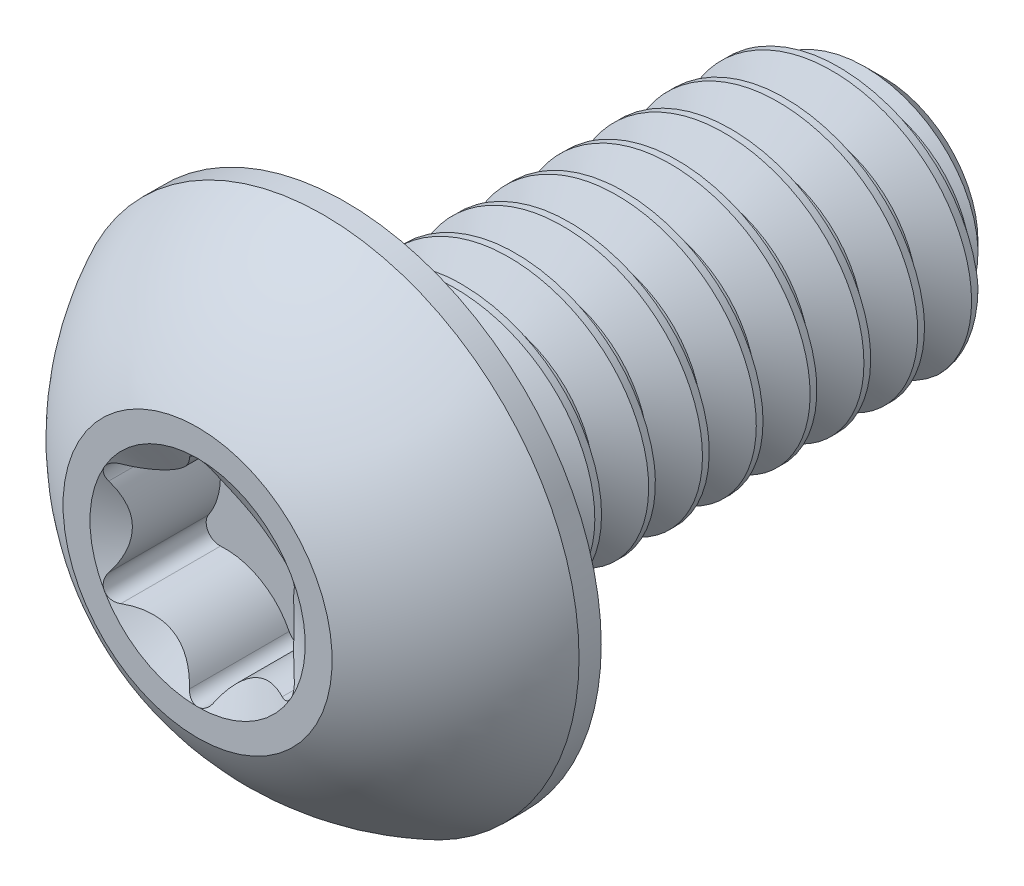
SolidWorks part; units mm, degrees
ref_plane "Front" through (0, 0, 0) normal (0, 0, 1) x (1, 0, 0)
ref_plane "Top" through (0, 0, 0) normal (0, 1, 0) x (1, 0, 0)
ref_plane "Right" through (0, 0, 0) normal (1, 0, 0) x (0, 0, -1)
sketch "Sketch1" plane through (0, 0, 0) normal (1, 0, 0) x (0, 0, -1)
  line L2 (1.1, 1) -> (5.1, 1)
  line L3 (5.1, 1) -> (5.1, 0)
  line L4 (5.1, 0) -> (1.1, 0)
  line L6 (0.935, 1.9) -> (1.1, 1.9) construction
  line L7 (5.1, 1) -> (5.1, -1) construction
  line L8 (0, 0) -> (1.1, 0) construction
  line L9 (1.1, 1.9) -> (1.1, -1.9) construction
  line L11 (1.1, 1) -> (1.1, 0)
  line L14 (0, 0) -> (0, 1) construction
  arc A3 (0, 1) -> (0.935, 1.9) centre (1.8632, 0) cw construction
  dimension "D1" = 0.165
revolve "Revolve1" add sketch "Sketch1" angle 360 mid plane about L4
sketch "Sketch3" plane through (0, 0, -5.1) normal (0, 0, -1) x (-1, 0, 0)
  circle A0 centre (0, 0) radius 1
curve "Helix/Spiral1" pitch 0.4 height 4.4 radius 1 centre (0, 0, -5.1) axis (0, 0, 1) start towards (0, 1, 0)
sketch "Sketch2" plane through (0, 0, 0) normal (1, 0, 0) x (0, 0, -1)
  line L0 (5.1, 1) -> (5.45, 1)
  line L1 (5.45, 1) -> (5.3, 0.7402)
  line L2 (5.3, 0.7402) -> (5.25, 0.7402)
  line L3 (5.25, 0.7402) -> (5.1, 1)
  line L4 (5.175, 0.8701) -> (5.375, 0.8701) construction
  dimension "D1" = 60
  dimension "D2" = 0.05
  dimension "D3" = 0.2
chamfer "Chamfer1" distance 0.3 angle 45 1 edges at (0, 1, -5.1)
sweep "Cut-Sweep1" cut profiles "Sketch2" path "Helix/Spiral1" align with end faces yes
sketch "Sketch7" plane through (0, 0, 0) normal (1, 0, 0) x (0, 0, -1)
  line L0 (0, 0) -> (0, 1) construction
  line L6 (0.935, 1.9) -> (1.1, 1.9) construction
  line L8 (0, 0) -> (1.1, 0) construction
  line L11 (1.1, 1.9) -> (1.1, -1.9) construction
  line L12 (0.935, 1.9) -> (1.1, 1.9)
  line L13 (0, 0) -> (1.1, 0)
  line L15 (1.1, 1.9) -> (1.1, 0)
  line L16 (0, 1) -> (0, 0)
  arc A2 (0.935, 1.9) -> (0, 1) centre (1.8632, 0) ccw construction
  arc A3 (0.935, 1.9) -> (0, 1) centre (1.8632, 0) ccw
revolve "Revolve2" add sketch "Sketch7" angle 360 mid plane about L13
sketch "Sketch5" plane through (0, 0, 0) normal (0, 0, 1) x (1, 0, 0)
  line L0 (2.6125, 0) -> (-2.6125, 0) construction
  line L2 (0, 0) -> (-0.6928, 0.4)
  line L3 (0, 0) -> (-0.6928, -0.4)
  line L4 (0, 0.8) -> (0, 0.7) construction
  line L5 (0, 0.7) -> (0, 0.6) construction
  circle A0 centre (0, 0) radius 0.6 construction
  circle A1 centre (0, 0) radius 0.7 construction
  circle A2 centre (0, 0) radius 0.8 construction
  arc A3 (-0.6894, 0.2944) -> (-0.6894, -0.2944) centre (-1.1298, 0) cw
  arc A4 (-0.6894, 0.2944) -> (-0.6928, 0.4) centre (-0.6062, 0.35) cw
  arc A5 (-0.6894, -0.2944) -> (-0.6928, -0.4) centre (-0.6062, -0.35) ccw
  dimension "D4" = 1.2
  dimension "D2" = 1.6
  dimension "D1" = 30
extrude "Cut-Extrude2" cut sketch "Sketch5" against normal blind 0.77
pattern_circular "CirPattern1" count 6 over 360 of "Cut-Extrude2"
sketch "Sketch11" plane through (0, 0, 0) normal (0, 0, 1) x (1, 0, 0)
  circle A0 centre (0, 0) radius 0.8 construction
  circle A1 centre (0, 0) radius 0.8
extrude "Cut-Extrude3" cut sketch "Sketch11" against normal blind 0.77 draft 60
sketch "Sketch9" [suppressed] plane through (0, 0, -1.4986) normal (0, 0, 1) x (1, 0, 0)
  circle A2 centre (0, 0) radius 1.4224
extrude "Boss-Extrude2" [suppressed] add sketch "Sketch9" against normal offset from surface (7.0104 mm away) 31.75 up to face at (0, 0.7, -5.1)
sketch "Sketch10" plane through (0, 0, 0) normal (1, 0, 0) x (0, 0, -1)
  line L0 (5.1, 1) -> (5.1, -1) construction
  point P0 (4.5, -1)
  dimension "D1" = 0.6
equation "\"D3@Helix/Spiral1\" = \"Lg@Sketch1\" + \"D4@Helix/Spiral1\""
equation "\"D2@Sketch2\" = \"D4@Helix/Spiral1\" * .125"
equation "\"D3@Sketch2\" = \"D4@Helix/Spiral1\" * .5"
equation "\"D1@Chamfer1\" = \"D4@Helix/Spiral1\" * .75"
equation "\"D1@Cut-Extrude2\" = \"Head Ht@Sketch1\" * .7"
equation "\"D1@Sketch1\" = \"Head Ht@Sketch1\" * .15"
equation "\"D1@Sketch10\" = \"D4@Helix/Spiral1\" * 1.5"
equation "\"D1@Cut-Extrude3\" = \"D1@Cut-Extrude2\""
equation "\"D2@Sketch5\" = \"Dia@Sketch1\" * .8"
equation "\"D4@Sketch5\" = \"D2@Sketch5\" * .75"
